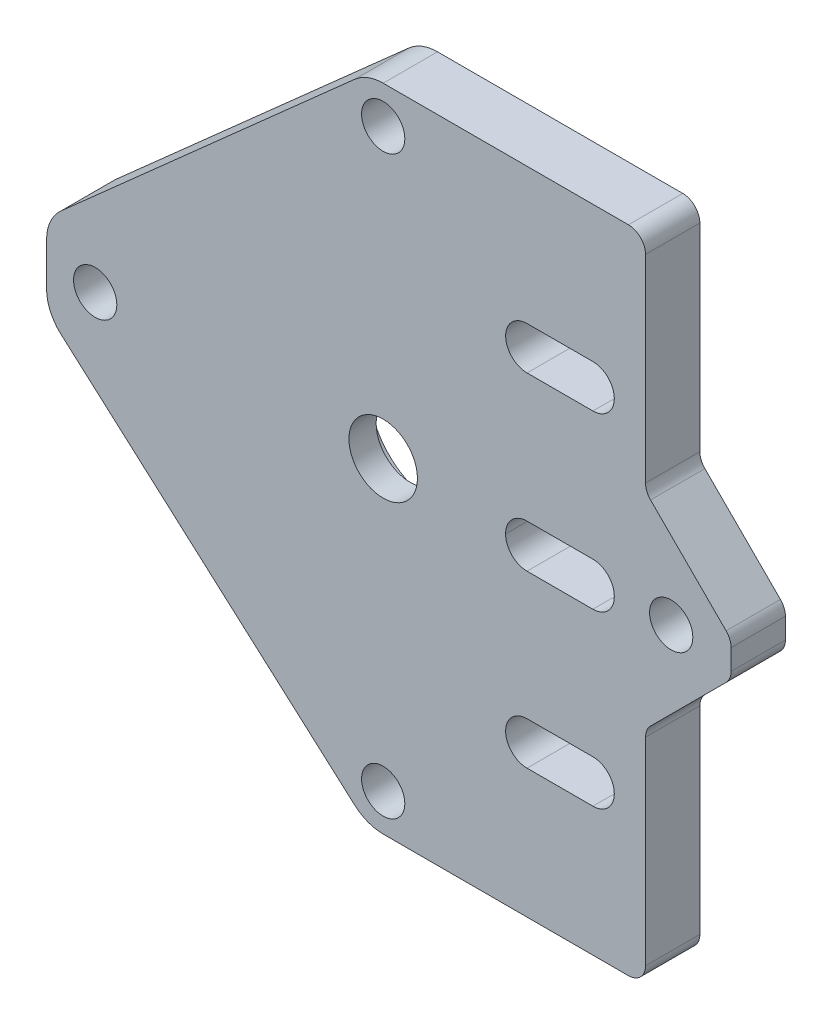
SolidWorks part; units mm, degrees
ref_plane "Front Plane" through (0, 0, 0) normal (0, 0, 1) x (1, 0, 0)
ref_plane "Top Plane" through (0, 0, 0) normal (0, 1, 0) x (1, 0, 0)
ref_plane "Right Plane" through (0, 0, 0) normal (1, 0, 0) x (0, 0, -1)
sketch "Sketch1" plane through (0, 0, 0) normal (0, 0, 1) x (1, 0, 0)
  line L0 (12.9983, -19.5801) -> (-20.66, -19.5801) construction
  line L1 (8, -57.5801) -> (-20.66, -57.5801)
  line L2 (10, -55.5801) -> (10, -32.435)
  line L3 (8, 18.4199) -> (-20.66, 18.4199)
  line L4 (-60, -17.0801) -> (-60, -22.0801)
  line L5 (-20.66, -53.2384) -> (-20.66, 14.0504) construction
  line L6 (-23.9803, 17.1582) -> (-58.3203, -13.3418)
  line L8 (-23.9803, -56.3185) -> (-58.3203, -25.8185)
  line L9 (10, 16.4199) -> (10, -6.7253)
  line L10 (-20.66, 14.0504) -> (-20.66, 18.4199) construction
  line L12 (-20.66, -53.2384) -> (-20.66, -57.5801) construction
  line L14 (-20.66, -19.5801) -> (-54.3183, -19.5801) construction
  line L16 (-54.3183, -19.5801) -> (-60, -19.5801) construction
  line L23 (10.5859, -31.0206) -> (19.4141, -22.1943)
  line L24 (20, -20.7799) -> (20, -18.3803)
  line L25 (19.4141, -16.966) -> (10.5859, -8.1396)
  line L28 (12.9983, -19.5801) -> (20, -19.5801) construction
  circle A0 centre (-20.66, -19.5801) radius 4
  circle A1 centre (-54.3183, -19.5801) radius 2.5277
  circle A2 centre (-20.66, 14.0504) radius 2.5277
  circle A3 centre (12.9983, -19.5801) radius 2.5277
  circle A4 centre (-20.66, -53.2384) radius 2.5277
  arc A5 (10.5859, -8.1396) -> (10, -6.7253) centre (12, -6.7253) cw
  arc A6 (20, -18.3803) -> (19.4141, -16.966) centre (18, -18.3803) ccw
  arc A7 (19.4141, -22.1943) -> (20, -20.7799) centre (18, -20.7799) ccw
  arc A8 (10, -32.435) -> (10.5859, -31.0206) centre (12, -32.435) cw
  arc A9 (-60, -22.0801) -> (-58.3203, -25.8185) centre (-55, -22.0801) ccw
  arc A10 (-23.9803, 17.1582) -> (-20.66, 18.4199) centre (-20.66, 13.4199) cw
  arc A11 (-60, -17.0801) -> (-58.3203, -13.3418) centre (-55, -17.0801) cw
  arc A12 (-23.9803, -56.3185) -> (-20.66, -57.5801) centre (-20.66, -52.5801) ccw
  arc A13 (10, 16.4199) -> (8, 18.4199) centre (8, 16.4199) ccw
  arc A14 (10, -55.5801) -> (8, -57.5801) centre (8, -55.5801) cw
  point P24 (-49.574, 10.4211)
  point P58 (10, -7.5538)
  point P65 (-49.574, -49.5814)
  point P67 (-26.66, 18.5627)
  point P74 (-26.66, -56.4373)
  dimension "D3" = 8
  dimension "D6" = 2
  dimension "D7" = 76
  dimension "D10" = 33.6583
  dimension "D11" = 5.0555
  dimension "D13" = 2
  dimension "D14" = 5
  dimension "D15" = 5
  dimension "D12" = 4.3417
  dimension "D2" = 10
  dimension "D4" = 30.66
  dimension "D5" = 70
  dimension "D8" = 5
  dimension "D9" = 67.2888
  dimension "D16" = 23.1451
extrude "Boss-Extrude1" add sketch "Sketch1" along normal blind 6.35
hole_wizard "Ø5.0mm Dowel Slot1" positions "Sketch3" profile "Sketch2" size "Ø5.0" standard "ANSI Metric" slot yes
sketch "Sketch3" plane through (0, 0, 6.35) normal (0, 0, 1) x (1, 0, 0)
  line L0 (-6.35, -40) -> (6.35, -40) construction
  line L1 (0, -20) -> (0, 0) construction
  line L2 (0, 0) -> (-3.8, 0) construction
  line L4 (0, -20) -> (0, -40) construction
  point P0 (0, -40)
  point P5 (0, -20.0674)
  point P7 (0, 0)
  point P9 (0, -20)
  dimension "D1" = 12.7
sketch "Sketch2" plane through (0, -40, 6.35) normal (1, 0, 0) x (0, -1, 0)
  line L0 (0, 0) -> (0, 11.5022)
  line L1 (0, 11.5022) -> (2.5, 10)
  line L2 (2.5, 10) -> (2.5, 0)
  line L5 (2.5, 0) -> (0, 0)
  line L10 (0, 11.5022) -> (-2.5, 10) construction
  line L11 (0, -6.35) -> (0, 107.95) construction
  dimension "Hole Dia." = 5
  dimension "Hole Depth" = 10
  dimension "Drill Angle" = 118
sketch "Sketch4" plane through (0, 0, 0) normal (0, 0, -1) x (-1, 0, 0)
  circle A0 centre (20.66, -19.5801) radius 8
  circle A1 centre (20.66, -19.5801) radius 4.9268 construction
  dimension "D1" = 16
extrude "Cut-Extrude1" cut sketch "Sketch4" against normal blind 3.175
